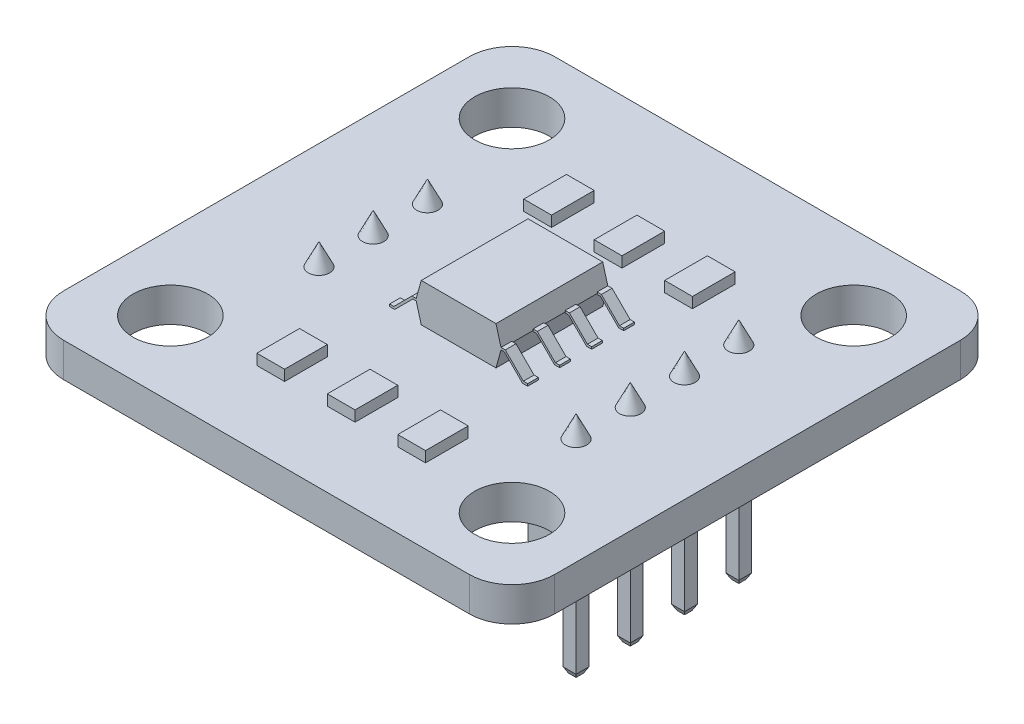
SolidWorks part; units mm, degrees
material "ABS"
ref_plane "정면" through (0, 0, 0) normal (0, 0, 1) x (1, 0, 0)
ref_plane "윗면" through (0, 0, 0) normal (0, 1, 0) x (1, 0, 0)
ref_plane "우측면" through (0, 0, 0) normal (1, 0, 0) x (0, 0, -1)
sketch "스케치1" plane through (0, 0, 0) normal (0, 1, 0) x (1, 0, 0)
  line L1 (11.5, -11.5) -> (-11.5, -11.5)
  line L2 (11.5, -11.5) -> (11.5, 11.5)
  line L3 (11.5, 11.5) -> (-11.5, 11.5)
  line L4 (-11.5, -11.5) -> (-11.5, 11.5)
  line L5 (11.5, -11.5) -> (-11.5, 11.5) construction
  line L6 (11.5, 11.5) -> (-11.5, -11.5) construction
  point P0 (0, 0)
  dimension "D1" = 23
  dimension "D2" = 23
extrude "보스-돌출1" add sketch "스케치1" along normal blind 1.6
sketch "스케치2" plane through (0, 1.6, 0) normal (0, 1, 0) x (1, 0, 0)
  line L1 (8, -8) -> (-8, -8) construction
  line L2 (8, -8) -> (8, 8) construction
  line L3 (8, 8) -> (-8, 8) construction
  line L4 (-8, -8) -> (-8, 8) construction
  line L5 (8, -8) -> (-8, 8) construction
  line L6 (8, 8) -> (-8, -8) construction
  circle A0 centre (-8, 8) radius 1.75
  circle A1 centre (8, 8) radius 1.75
  circle A2 centre (8, -8) radius 1.75
  circle A3 centre (-8, -8) radius 1.75
  point P0 (0, 0)
  dimension "D3" = 3.5
  dimension "D1" = 16
  dimension "D2" = 16
extrude "컷-돌출1" cut sketch "스케치2" against normal through all
fillet "필렛1" radius 2 4 edges at (11.5, 0.8, -11.5) (11.5, 0.8, 11.5) (-11.5, 0.8, 11.5) (-11.5, 0.8, -11.5)
sketch "스케치4" plane through (0, 1.6, 0) normal (0, 1, 0) x (1, 0, 0)
  line L1 (2, -2.5) -> (-2, -2.5)
  line L2 (2, -2.5) -> (2, 2.5)
  line L3 (2, 2.5) -> (-2, 2.5)
  line L4 (-2, -2.5) -> (-2, 2.5)
  line L5 (2, -2.5) -> (-2, 2.5) construction
  line L6 (2, 2.5) -> (-2, -2.5) construction
  point P0 (0, 0)
  dimension "D1" = 5
  dimension "D2" = 4
extrude "보스-돌출2" add sketch "스케치4" along normal blind 1.8
sketch "스케치5" plane through (0, 0, 2.5) normal (0, 0, 1) x (1, 0, 0)
  line L0 (-1.75, 1.6) -> (-2, 2.5)
  line L1 (-2, 1.6) -> (2, 1.6) construction
  line L2 (-2, 3.4) -> (-2, 1.6) construction
  line L3 (-2, 2.5) -> (-1.75, 3.4)
  line L4 (-2, 3.4) -> (2, 3.4) construction
  line L5 (-1.75, 3.4) -> (-2, 3.4)
  line L6 (-2, 3.4) -> (-2, 1.6)
  line L7 (-9.5, 1.6) -> (9.5, 1.6) construction
  line L8 (-2, 1.6) -> (-1.75, 1.6)
  line L9 (2, 3.4) -> (2, 1.6)
  line L10 (2, 1.6) -> (1.75, 1.6)
  line L11 (1.75, 1.6) -> (2, 2.5)
  line L12 (2, 2.5) -> (1.75, 3.4)
  line L13 (1.75, 3.4) -> (2, 3.4)
  line M3 (-2, 1.6) -> (2, 1.6)
  line M4 (2, 1.6) -> (2, 3.4)
  line M5 (2, 3.4) -> (-2, 3.4)
  line M6 (-2, 3.4) -> (-2, 1.6)
  dimension "D1" = 0.25
extrude "컷-돌출2" cut sketch "스케치5" against normal through all contours L3 M6 M5 | L0 M3 M6 | L11 M3 M4 | L12 L9 M5 region at (-1.9167, 1.9, 2.5) region at (-1.9167, 3.1, 2.5) region at (1.9167, 1.9, 2.5) region at (1.9167, 3.1, 2.5)
sketch "스케치6" plane through (0, 0, 2.5) normal (0, 0, 1) x (1, 0, 0)
  line L0 (-1.9861, 2.55) -> (-1.9861, 2.45)
  line L1 (-1.9861, 2.45) -> (-2.1447, 2.45)
  line L2 (-2.1447, 2.45) -> (-2.9947, 1.6)
  line L3 (-9.5, 1.6) -> (9.5, 1.6) construction
  line L4 (-2.9947, 1.6) -> (-3.232, 1.6)
  line L5 (-3.232, 1.6) -> (-3.232, 1.7041)
  line L6 (-3.232, 1.7041) -> (-3.032, 1.7041)
  line L7 (-3.032, 1.7041) -> (-2.1861, 2.55)
  line L8 (-2.1861, 2.55) -> (-1.9861, 2.55)
  line L9 (0, 3.4) -> (0, 1.6) construction
  line L10 (-1.75, 3.4) -> (1.75, 3.4) construction
  line L11 (3.032, 1.7041) -> (2.1861, 2.55)
  line L12 (3.232, 1.7041) -> (3.032, 1.7041)
  line L13 (3.232, 1.6) -> (3.232, 1.7041)
  line L14 (2.9947, 1.6) -> (3.232, 1.6)
  line L15 (2.1447, 2.45) -> (2.9947, 1.6)
  line L16 (1.9861, 2.45) -> (2.1447, 2.45)
  line L17 (1.9861, 2.55) -> (1.9861, 2.45)
  line L18 (2.1861, 2.55) -> (1.9861, 2.55)
  line L20 (-2, 2.5) -> (-1.75, 3.4) construction
  line L21 (-1.75, 1.6) -> (-2, 2.5) construction
  dimension "D1" = 135
  dimension "D2" = 0.1
  dimension "D3" = 0.1041
  dimension "D4" = 0.1
  dimension "D5" = 0.2
  dimension "D6" = 0.2
extrude "보스-돌출3" add sketch "스케치6" against normal blind 0.5
pattern_linear "선형 패턴1" count 4 spacing 1.5 along (0, 0, -1) of "보스-돌출3"
sketch "스케치8" plane through (0, 1.6, 0) normal (0, 1, 0) x (1, 0, 0)
  line L0 (1.75, 2.5) -> (-1.75, 2.5) construction
  line L1 (-3.95, 6.5) -> (-2.65, 6.5)
  line L2 (-3.95, 6.5) -> (-3.95, 4.5)
  line L3 (-3.95, 4.5) -> (-2.65, 4.5)
  line L4 (-2.65, 6.5) -> (-2.65, 4.5)
  line L5 (-3.95, 6.5) -> (-2.65, 4.5) construction
  line L6 (-3.95, 4.5) -> (-2.65, 6.5) construction
  line L7 (0.65, 4.5) -> (-0.65, 4.5)
  line L8 (0.65, 4.5) -> (0.65, 6.5)
  line L9 (0.65, 6.5) -> (-0.65, 6.5)
  line L10 (-0.65, 4.5) -> (-0.65, 6.5)
  line L11 (0.65, 4.5) -> (-0.65, 6.5) construction
  line L12 (0.65, 6.5) -> (-0.65, 4.5) construction
  line L13 (3.95, 4.5) -> (2.65, 4.5)
  line L14 (3.95, 4.5) -> (3.95, 6.5)
  line L15 (3.95, 6.5) -> (2.65, 6.5)
  line L16 (2.65, 4.5) -> (2.65, 6.5)
  line L17 (3.95, 4.5) -> (2.65, 6.5) construction
  line L18 (3.95, 6.5) -> (2.65, 4.5) construction
  line L19 (-2.65, -8) -> (-3.95, -8)
  line L20 (-2.65, -8) -> (-2.65, -6)
  line L21 (-2.65, -6) -> (-3.95, -6)
  line L22 (-3.95, -8) -> (-3.95, -6)
  line L23 (-2.65, -8) -> (-3.95, -6) construction
  line L24 (-2.65, -6) -> (-3.95, -8) construction
  line L25 (0.65, -8) -> (-0.65, -8)
  line L26 (0.65, -8) -> (0.65, -6)
  line L27 (0.65, -6) -> (-0.65, -6)
  line L28 (-0.65, -8) -> (-0.65, -6)
  line L29 (0.65, -8) -> (-0.65, -6) construction
  line L30 (0.65, -6) -> (-0.65, -8) construction
  line L31 (3.95, -8) -> (2.65, -8)
  line L32 (3.95, -8) -> (3.95, -6)
  line L33 (3.95, -6) -> (2.65, -6)
  line L34 (2.65, -8) -> (2.65, -6)
  line L35 (3.95, -8) -> (2.65, -6) construction
  line L36 (3.95, -6) -> (2.65, -8) construction
  line L37 (-1.75, -2.5) -> (1.75, -2.5) construction
  point P0 (-3.3, 5.5)
  point P5 (0, 5.5)
  point P10 (3.3, 5.5)
  point P15 (-3.3, -7)
  point P20 (0, -7)
  point P25 (3.3, -7)
  dimension "D1" = 1.3
  dimension "D2" = 2
  dimension "D3" = 2
  dimension "D4" = 2
  dimension "D5" = 2
  dimension "D6" = 3.5
extrude "보스-돌출4" add sketch "스케치8" along normal blind 0.5
sketch "스케치9" plane through (0, 1.6, 0) normal (0, 1, 0) x (1, 0, 0)
  line L0 (-6.5, 2.54) -> (-6.5, -2.54) construction
  line L1 (6.5, 1.58) -> (6.5, -3.5) construction
  line L5 (-9.5, -11.5) -> (9.5, -11.5) construction
  circle A0 centre (-6.5, 2.54) radius 0.5
  circle A1 centre (-6.5, 0) radius 0.5
  circle A2 centre (-6.5, -2.54) radius 0.5
  circle A3 centre (6.5, -0.96) radius 0.5
  circle A4 centre (6.5, 1.58) radius 0.5
  circle A5 centre (6.5, 4.12) radius 0.5
  circle A6 centre (6.5, -3.5) radius 0.5
  dimension "D3" = 1
  dimension "D1" = 6.5
  dimension "D2" = 6.5
  dimension "D4" = 2.54
  dimension "D5" = 2.54
  dimension "D6" = 8
extrude "보스-돌출5" add sketch "스케치9" along normal blind 1
chamfer "모따기1" distance 1 angle 26 7 edges at (6.5, 2.6, -3.62) (6.5, 2.6, -1.08) (6.5, 2.6, 1.46) (6.5, 2.6, 4) (-6.5, 2.6, -2.04) (-6.5, 2.6, 0.5) (-6.5, 2.6, 3.04) first distance on face at (6.5, 2.6, -3.62) first distance on face at (6.5, 2.6, -1.08) first distance on face at (6.5, 2.6, 1.46) first distance on face at (6.5, 2.6, 4) first distance on face at (-6.5, 2.6, -2.04) first distance on face at (-6.5, 2.6, 0.5) first distance on face at (-6.5, 2.6, 3.04)
sketch "스케치10" plane through (0, 0, 0) normal (0, -1, 0) x (1, 0, 0)
  line L0 (-7.77, 3.51) -> (-7.77, 1.57)
  line L1 (-7.77, 1.57) -> (-7.47, 1.27)
  line L2 (-7.47, 1.27) -> (-5.53, 1.27)
  line L3 (-5.53, 1.27) -> (-5.23, 1.57)
  line L4 (-5.23, 1.57) -> (-5.23, 3.51)
  line L5 (-5.23, 3.51) -> (-5.53, 3.81)
  line L6 (-5.53, 3.81) -> (-7.47, 3.81)
  line L7 (-7.47, 3.81) -> (-7.77, 3.51)
  line L8 (5.23, 4.47) -> (5.23, 2.53)
  line L9 (5.23, 2.53) -> (5.53, 2.23)
  line L10 (5.53, 2.23) -> (7.47, 2.23)
  line L11 (7.47, 2.23) -> (7.77, 2.53)
  line L12 (7.77, 2.53) -> (7.77, 4.47)
  line L13 (7.77, 4.47) -> (7.47, 4.77)
  line L14 (7.47, 4.77) -> (5.53, 4.77)
  line L15 (5.53, 4.77) -> (5.23, 4.47)
  line L16 (-6.5, 2.54) -> (-6.5, 3.81) construction
  line L17 (-6.5, 2.54) -> (-5.23, 2.54) construction
  line L18 (5.23, 3.5) -> (6.5, 3.5) construction
  line L19 (6.5, 3.5) -> (6.5, 4.77) construction
  dimension "D1" = 2.54
  dimension "D2" = 2.54
  dimension "D3" = 135
  dimension "D4" = 0.3
extrude "보스-돌출6" add sketch "스케치10" along normal blind 2.4
pattern_linear "선형 패턴2" count 3 spacing 2.54 along (0, 0, -1) of "보스-돌출6"
sketch "스케치11" plane through (0, 0, 0) normal (0, -1, 0) x (1, 0, 0)
  line L0 (5.53, -2.85) -> (7.47, -2.85)
  line L1 (7.47, -2.85) -> (7.77, -3.15)
  line L2 (7.77, -3.15) -> (7.77, -5.09)
  line L3 (7.77, -5.09) -> (7.47, -5.39)
  line L4 (7.47, -5.39) -> (5.53, -5.39)
  line L5 (5.53, -5.39) -> (5.23, -5.09)
  line L6 (5.23, -5.09) -> (5.23, -3.15)
  line L7 (5.23, -3.15) -> (5.53, -2.85)
  line L8 (5.23, -0.61) -> (5.23, -2.55) construction
  line L9 (5.23, -2.55) -> (5.53, -2.85) construction
extrude "보스-돌출7" add sketch "스케치11" along normal up to surface (2.4 mm away) up to face at (6.5, -2.4, 0.96)
sketch "스케치12" plane through (0, -2.4, 0) normal (0, -1, 0) x (1, 0, 0)
  line L1 (-6.8, 2.24) -> (-6.2, 2.24)
  line L2 (-6.8, 2.24) -> (-6.8, 2.84)
  line L3 (-6.8, 2.84) -> (-6.2, 2.84)
  line L4 (-6.2, 2.24) -> (-6.2, 2.84)
  line L5 (-6.8, 2.24) -> (-6.2, 2.84) construction
  line L6 (-6.8, 2.84) -> (-6.2, 2.24) construction
  line L11 (-6.8, -0.3) -> (-6.8, 0.3)
  line L12 (-6.8, -0.3) -> (-6.2, -0.3)
  line L13 (-6.2, -0.3) -> (-6.2, 0.3)
  line L18 (-6.8, 0.3) -> (-6.2, 0.3)
  line L19 (-6.8, -2.84) -> (-6.8, -2.24)
  line L24 (-6.8, -2.84) -> (-6.2, -2.84)
  line L25 (-6.2, -2.84) -> (-6.2, -2.24)
  line L30 (-6.8, -2.24) -> (-6.2, -2.24)
  line L31 (6.2, 0.66) -> (6.2, 1.26)
  line L36 (6.2, 3.2) -> (6.8, 3.2)
  line L37 (6.2, 3.2) -> (6.2, 3.8)
  line L42 (6.2, 3.8) -> (6.8, 3.8)
  line L43 (6.8, 3.2) -> (6.8, 3.8)
  line L44 (6.2, 3.2) -> (6.8, 3.8) construction
  line L45 (6.2, 3.8) -> (6.8, 3.2) construction
  line L46 (6.2, 0.66) -> (6.8, 0.66)
  line L47 (6.8, 0.66) -> (6.8, 1.26)
  line L48 (6.2, 1.26) -> (6.8, 1.26)
  line L49 (6.2, -1.88) -> (6.2, -1.28)
  line L50 (6.2, -1.88) -> (6.8, -1.88)
  line L51 (6.8, -1.88) -> (6.8, -1.28)
  line L52 (6.2, -1.28) -> (6.8, -1.28)
  line L53 (6.2, -4.42) -> (6.2, -3.82)
  line L54 (6.2, -4.42) -> (6.8, -4.42)
  line L55 (6.8, -4.42) -> (6.8, -3.82)
  line L56 (6.2, -3.82) -> (6.8, -3.82)
  point P0 (-6.5, 2.54)
  point P15 (6.5, 3.5)
  dimension "D1" = 0.6
  dimension "D3" = 2.54
  dimension "D5" = 2.54
  dimension "D2" = 3
  dimension "D4" = 4
extrude "보스-돌출8" add sketch "스케치12" along normal blind 5.5
chamfer "모따기2" distance 0.25 angle 26 28 edges at (6.5, -7.9, 3.2) (6.2, -7.9, 3.5) (6.5, -7.9, 3.8) (6.8, -7.9, 3.5) (6.8, -7.9, 0.96) (6.5, -7.9, 0.66) (6.2, -7.9, 0.96) (6.5, -7.9, 1.26) (6.8, -7.9, -1.58) (6.5, -7.9, -1.88) (6.2, -7.9, -1.58) (6.5, -7.9, -1.28) (6.8, -7.9, -4.12) (6.5, -7.9, -4.42) (6.2, -7.9, -4.12) (6.5, -7.9, -3.82) (-6.2, -7.9, -2.54) (-6.5, -7.9, -2.84) (-6.8, -7.9, -2.54) (-6.5, -7.9, -2.24) (-6.2, -7.9, 0) (-6.5, -7.9, -0.3) (-6.8, -7.9, 0) (-6.5, -7.9, 0.3) (-6.5, -7.9, 2.24) (-6.8, -7.9, 2.54) (-6.5, -7.9, 2.84) (-6.2, -7.9, 2.54) first distance on face at (6.5, -5.15, 3.2) first distance on face at (6.2, -5.15, 3.5) first distance on face at (6.5, -5.15, 3.8) first distance on face at (6.8, -5.15, 3.5) first distance on face at (6.8, -5.15, 0.96) first distance on face at (6.5, -5.15, 0.66) first distance on face at (6.2, -5.15, 0.96) first distance on face at (6.5, -5.15, 1.26) first distance on face at (6.8, -5.15, -1.58) first distance on face at (6.5, -5.15, -1.88) first distance on face at (6.2, -5.15, -1.58) first distance on face at (6.5, -5.15, -1.28) first distance on face at (6.8, -5.15, -4.12) first distance on face at (6.5, -5.15, -4.42) first distance on face at (6.2, -5.15, -4.12) first distance on face at (6.5, -5.15, -3.82) first distance on face at (-6.2, -5.15, -2.54) first distance on face at (-6.5, -5.15, -2.84) first distance on face at (-6.8, -5.15, -2.54) first distance on face at (-6.5, -5.15, -2.24) first distance on face at (-6.2, -5.15, 0) first distance on face at (-6.5, -5.15, -0.3) first distance on face at (-6.8, -5.15, 0) first distance on face at (-6.5, -5.15, 0.3) first distance on face at (-6.5, -5.15, 2.24) first distance on face at (-6.8, -5.15, 2.54) first distance on face at (-6.5, -5.15, 2.84) first distance on face at (-6.2, -5.15, 2.54)
